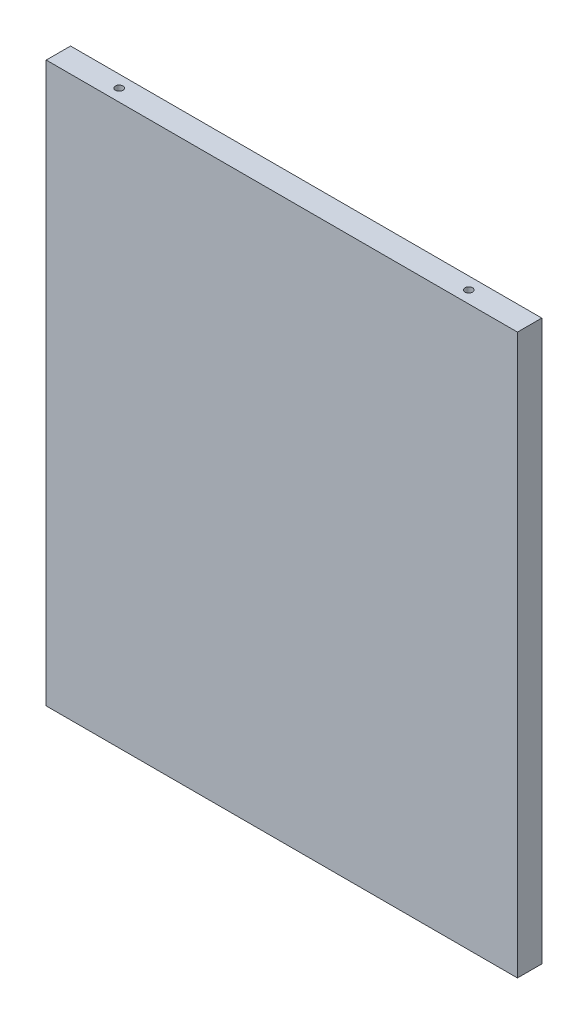
SolidWorks part; units mm, degrees
material "ДСП"
ref_plane "Спереди" through (0, 0, 0) normal (0, 0, 1) x (1, 0, 0)
ref_plane "Сверху" through (0, 0, 0) normal (0, 1, 0) x (1, 0, 0)
ref_plane "Справа" through (0, 0, 0) normal (1, 0, 0) x (0, 0, -1)
sketch "Эскиз1" plane through (0, 0, 0) normal (0, 0, 1) x (1, 0, 0)
  line L1 (0, 0) -> (310, 0)
  line L2 (0, 0) -> (0, 368)
  line L3 (0, 368) -> (310, 368)
  line L4 (310, 0) -> (310, 368)
  dimension "D1" = 368
  dimension "D2" = 310
extrude "Придание толщины" add sketch "Эскиз1" along normal blind 16
sketch "Эскиз3" plane through (0, 0, 16) normal (0, 0, 1) x (1, 0, 0)
  line L0 (0, 368) -> (0, 0) construction
  line L1 (0, 0) -> (310, 0) construction
  circle A0 centre (0, 0) radius 4
  dimension "D1" = 8
  dimension "D2" = 0
  dimension "D3" = 0
extrude "Отверстие 1" [suppressed] cut sketch "Эскиз3" against normal blind 16
sketch "Эскиз4" plane through (0, 0, 16) normal (0, 0, 1) x (1, 0, 0)
  line L0 (0, 368) -> (0, 0) construction
  line L1 (0, 0) -> (310, 0) construction
  circle A0 centre (0, 0) radius 4
  dimension "D2" = 0
  dimension "D3" = 8
extrude "Отверстие 2" [suppressed] cut sketch "Эскиз4" against normal blind 16
sketch "Эскиз5" plane through (0, 0, 16) normal (0, 0, 1) x (1, 0, 0)
  line L0 (0, 368) -> (0, 0) construction
  line L1 (0, 0) -> (310, 0) construction
  circle A0 centre (0, 0) radius 4
  dimension "D1" = 8
extrude "Отверстие 3" [suppressed] cut sketch "Эскиз5" against normal blind 16
sketch "Эскиз6" plane through (0, 0, 16) normal (0, 0, 1) x (1, 0, 0)
  line L0 (0, 368) -> (0, 0) construction
  line L1 (0, 0) -> (310, 0) construction
  circle A0 centre (0, 0) radius 4
  dimension "D1" = 8
extrude "Отверстие 4" [suppressed] cut sketch "Эскиз6" against normal blind 16
sketch "Эскиз7" plane through (0, 0, 16) normal (0, 0, 1) x (1, 0, 0)
  line L0 (0, 368) -> (0, 0) construction
  line L1 (0, 0) -> (310, 0) construction
  circle A0 centre (0, 0) radius 4
  dimension "D1" = 8
extrude "Отверстие 5" [suppressed] cut sketch "Эскиз7" against normal blind 16
sketch "Эскиз8" plane through (0, 0, 16) normal (0, 0, 1) x (1, 0, 0)
  line L0 (0, 368) -> (0, 0) construction
  line L1 (0, 0) -> (310, 0) construction
  circle A0 centre (0, 0) radius 4
  dimension "D1" = 8
extrude "Отверстие 6" [suppressed] cut sketch "Эскиз8" against normal blind 16
sketch "Эскиз9" plane through (0, 0, 16) normal (0, 0, 1) x (1, 0, 0)
  line L0 (0, 368) -> (0, 0) construction
  line L1 (0, 0) -> (310, 0) construction
  circle A0 centre (0, 0) radius 4
  dimension "D1" = 8
extrude "Отверстие 7" [suppressed] cut sketch "Эскиз9" against normal blind 16
sketch "Эскиз10" plane through (0, 0, 16) normal (0, 0, 1) x (1, 0, 0)
  line L0 (0, 368) -> (0, 0) construction
  line L1 (0, 0) -> (310, 0) construction
  circle A0 centre (0, 0) radius 4
  dimension "D1" = 8
extrude "Отверстие 8" [suppressed] cut sketch "Эскиз10" against normal blind 16
sketch "Эскиз27" plane through (0, 0, 16) normal (0, 0, 1) x (1, 0, 0)
  line L2 (0, 368) -> (0, 0) construction
  line L3 (0, 0) -> (310, 0) construction
  circle A0 centre (0, 0) radius 4
  dimension "D1" = 8
  dimension "D3" = 0
extrude "Отверстие 9" [suppressed] cut sketch "Эскиз27" against normal blind 10
sketch "Эскиз29" plane through (0, 0, 16) normal (0, 0, 1) x (1, 0, 0)
  line L2 (0, 368) -> (0, 0) construction
  line L3 (0, 0) -> (310, 0) construction
  circle A0 centre (0, 0) radius 4
  dimension "D1" = 8
extrude "Отверстие 10" [suppressed] cut sketch "Эскиз29" against normal blind 10
sketch "Эскиз30" plane through (0, 0, 16) normal (0, 0, 1) x (1, 0, 0)
  line L1 (0, 0) -> (310, 0) construction
  line L3 (0, 368) -> (0, 0) construction
  circle A0 centre (0, 0) radius 4
  dimension "D1" = 8
extrude "Отверстие 11" [suppressed] cut sketch "Эскиз30" against normal blind 10
sketch "Эскиз31" plane through (0, 0, 16) normal (0, 0, 1) x (1, 0, 0)
  line L2 (0, 0) -> (310, 0) construction
  line L3 (0, 368) -> (0, 0) construction
  circle A0 centre (0, 0) radius 4
  dimension "D1" = 8
extrude "Отверстие 12" [suppressed] cut sketch "Эскиз31" against normal blind 10
sketch "Эскиз11" plane through (0, 368, 0) normal (0, 1, 0) x (1, 0, 0)
  line L0 (0, -16) -> (0, 0) construction
  line L1 (310, -16) -> (0, -16) construction
  circle A0 centre (40, -8) radius 2.5
  dimension "D3" = 8
  dimension "D1" = 5
  dimension "D2" = 40
extrude "Отверстие А1" cut sketch "Эскиз11" against normal blind 37
sketch "Эскиз12" plane through (0, 368, 0) normal (0, 1, 0) x (1, 0, 0)
  line L1 (0, -16) -> (0, 0) construction
  line L2 (310, -16) -> (0, -16) construction
  circle A0 centre (270, -8) radius 2.5
  dimension "D3" = 8
  dimension "D1" = 5
  dimension "D2" = 270
extrude "Отверстие А2" cut sketch "Эскиз12" against normal blind 37
sketch "Эскиз13" plane through (0, 368, 0) normal (0, 1, 0) x (1, 0, 0)
  line L1 (0, -16) -> (0, 0) construction
  line L2 (310, -16) -> (0, -16) construction
  circle A0 centre (0, -16) radius 4
  dimension "D1" = 8
  dimension "D3" = 0
extrude "Отверстие А3" [suppressed] cut sketch "Эскиз13" against normal blind 20
sketch "Эскиз14" plane through (0, 368, 0) normal (0, 1, 0) x (1, 0, 0)
  line L0 (0, -16) -> (0, 0) construction
  line L1 (310, -16) -> (0, -16) construction
  circle A0 centre (0, -8) radius 4
  dimension "D1" = 8
  dimension "D3" = 8
extrude "Отверстие А4" [suppressed] cut sketch "Эскиз14" against normal blind 20
sketch "Эскиз15" plane through (310, 0, 0) normal (1, 0, 0) x (0, 0, -1)
  line L0 (-16, 368) -> (0, 368) construction
  line L1 (-16, 0) -> (-16, 368) construction
  circle A0 centre (-16, 368) radius 2.5
  dimension "D2" = 0
  dimension "D3" = 0
  dimension "D1" = 5
extrude "Отверстие В1" [suppressed] cut sketch "Эскиз15" against normal blind 37
sketch "Эскиз16" plane through (310, 0, 0) normal (1, 0, 0) x (0, 0, -1)
  line L0 (-16, 368) -> (0, 368) construction
  line L1 (-16, 0) -> (-16, 368) construction
  circle A0 centre (-16, 368) radius 2.5
  dimension "D1" = 5
extrude "Отверстие В2" [suppressed] cut sketch "Эскиз16" against normal blind 37
sketch "Эскиз17" plane through (310, 0, 0) normal (1, 0, 0) x (0, 0, -1)
  line L1 (-16, 368) -> (0, 368) construction
  line L2 (-16, 0) -> (-16, 368) construction
  circle A0 centre (-16, 368) radius 4
  dimension "D1" = 8
  dimension "D2" = 0
  dimension "D3" = 0
extrude "Отверстие В3" [suppressed] cut sketch "Эскиз17" against normal blind 20
sketch "Эскиз18" plane through (310, 0, 0) normal (1, 0, 0) x (0, 0, -1)
  line L0 (-16, 368) -> (0, 368) construction
  line L1 (-16, 0) -> (-16, 368) construction
  circle A0 centre (-16, 368) radius 4
  dimension "D3" = 0
  dimension "D1" = 0
  dimension "D2" = 8
extrude "Отверстие В4" [suppressed] cut sketch "Эскиз18" against normal blind 20
sketch "Эскиз19" plane through (0, 0, 0) normal (0, -1, 0) x (1, 0, 0)
  line L0 (310, 16) -> (310, 0) construction
  line L1 (0, 16) -> (310, 16) construction
  circle A0 centre (270, 8) radius 2.5
  dimension "D3" = 8
  dimension "D1" = 5
  dimension "D2" = 40
extrude "Отверстие С1" cut sketch "Эскиз19" against normal blind 37
sketch "Эскиз20" plane through (0, 0, 0) normal (0, -1, 0) x (1, 0, 0)
  line L0 (310, 16) -> (310, 0) construction
  line L1 (0, 16) -> (310, 16) construction
  circle A0 centre (40, 8) radius 2.5
  dimension "D3" = 8
  dimension "D2" = 5
  dimension "D1" = 270
extrude "Отверстие С2" cut sketch "Эскиз20" against normal blind 37
sketch "Эскиз21" plane through (0, 0, 0) normal (0, -1, 0) x (1, 0, 0)
  line L0 (310, 16) -> (310, 0) construction
  line L1 (0, 16) -> (310, 16) construction
  circle A0 centre (310, 16) radius 4
  dimension "D1" = 8
  dimension "D2" = 0
  dimension "D3" = 0
extrude "Отверстие С3" [suppressed] cut sketch "Эскиз21" against normal blind 20
sketch "Эскиз22" plane through (0, 0, 0) normal (0, -1, 0) x (1, 0, 0)
  line L0 (310, 16) -> (310, 0) construction
  line L1 (0, 16) -> (310, 16) construction
  circle A0 centre (310, 16) radius 4
  dimension "D1" = 8
  dimension "D2" = 0
  dimension "D3" = 0
extrude "Отверстие С4" [suppressed] cut sketch "Эскиз22" against normal blind 20
sketch "Эскиз23" plane through (0, 0, 0) normal (-1, 0, 0) x (0, 0, 1)
  line L0 (16, 0) -> (0, 0) construction
  line L1 (16, 368) -> (16, 0) construction
  circle A0 centre (16, 0) radius 2.5
  dimension "D2" = 0
  dimension "D3" = 0
  dimension "D1" = 5
extrude "Отверстие Д1" [suppressed] cut sketch "Эскиз23" against normal blind 37
sketch "Эскиз24" plane through (0, 0, 0) normal (-1, 0, 0) x (0, 0, 1)
  line L0 (16, 0) -> (0, 0) construction
  line L1 (16, 368) -> (16, 0) construction
  circle A0 centre (16, 0) radius 2.5
  dimension "D2" = 0
  dimension "D3" = 0
  dimension "D1" = 5
extrude "Отверстие Д2" [suppressed] cut sketch "Эскиз24" against normal blind 37
sketch "Эскиз25" plane through (0, 0, 0) normal (-1, 0, 0) x (0, 0, 1)
  line L0 (16, 0) -> (0, 0) construction
  line L1 (16, 368) -> (16, 0) construction
  circle A0 centre (16, 0) radius 4
  dimension "D1" = 8
  dimension "D2" = 0
  dimension "D3" = 0
extrude "Отверстие Д3" [suppressed] cut sketch "Эскиз25" against normal blind 20
sketch "Эскиз26" plane through (0, 0, 0) normal (-1, 0, 0) x (0, 0, 1)
  line L0 (16, 0) -> (0, 0) construction
  line L1 (16, 368) -> (16, 0) construction
  circle A0 centre (16, 0) radius 4
  dimension "D1" = 8
  dimension "D2" = 0
  dimension "D3" = 0
extrude "Отверстие Д4" [suppressed] cut sketch "Эскиз26" against normal blind 20
equation "\"D1@Придание толщины\" = \"Thick\""
equation "\"D2@Эскиз1\"=\"Width\""
equation "\"D1@Эскиз1\"=\"Height\""
equation "\"D1\" = 0"
equation "\"X1\" = 0"
equation "\"Y1\" = 0"
equation "\"H1\" = 0"
equation "\"D1@Эскиз3\"=\"D1\""
equation "\"D2@Эскиз3\"=\"X1\""
equation "\"D3@Эскиз3\"=\"Y1\""
equation "\"D1@Отверстие 1\"=\"H1\""
equation "\"D2\" = 0"
equation "\"X2\" = 0"
equation "\"Y2\" = 0"
equation "\"H2\" = 0"
equation "\"D3\" = 0"
equation "\"X3\" = 0"
equation "\"Y3\" = 0"
equation "\"H3\" = 0"
equation "\"D4\" = 0"
equation "\"X4\" = 0"
equation "\"Y4\" = 0"
equation "\"H4\" = 0"
equation "\"D5\" = 0"
equation "\"X5\" = 0"
equation "\"Y5\" = 0"
equation "\"H5\" = 0"
equation "\"D6\" = 0"
equation "\"X6\" = 0"
equation "\"Y6\" = 0"
equation "\"H6\" = 0"
equation "\"D7\" = 0"
equation "\"X7\" = 0"
equation "\"Y7\" = 0"
equation "\"H7\" = 0"
equation "\"D8\" = 0"
equation "\"X8\" = 0"
equation "\"Y8\" = 0"
equation "\"H8\" = 0"
equation "\"D3@Эскиз4\"=\"D2\""
equation "\"D1@Эскиз4\"=\"X2\""
equation "\"D2@Эскиз4\"=\"Y2\""
equation "\"D1@Отверстие 2\"=\"H2\""
equation "\"D2@Эскиз5\"=\"X3\""
equation "\"D1@Эскиз5\"=\"D3\""
equation "\"D3@Эскиз5\"=\"Y3\""
equation "\"D1@Отверстие 3\" = \"H3\""
equation "\"D1@Эскиз6\"=\"D4\""
equation "\"D2@Эскиз6\"=\"X4\""
equation "\"D3@Эскиз6\"=\"Y4\""
equation "\"D1@Отверстие 4\" = \"H4\""
equation "\"D1@Эскиз7\"=\"D5\""
equation "\"D2@Эскиз7\"=\"X5\""
equation "\"D3@Эскиз7\"=\"Y5\""
equation "\"D1@Отверстие 5\" = \"H5\""
equation "\"D1@Эскиз8\"=\"D6\""
equation "\"D2@Эскиз8\"=\"X6\""
equation "\"D3@Эскиз8\"=\"Y6\""
equation "\"D1@Отверстие 6\" = \"H6\""
equation "\"D1@Эскиз9\"=\"D7\""
equation "\"D2@Эскиз9\"=\"X7\""
equation "\"D3@Эскиз9\"=\"Y7\""
equation "\"D1@Отверстие 7\" = \"H7\""
equation "\"D1@Эскиз10\"=\"D8\""
equation "\"D2@Эскиз10\"=\"X8\""
equation "\"D3@Эскиз10\"=\"Y8\""
equation "\"D1@Отверстие 8\" = \"H8\""
equation "\"Отверстие 1\"= IIF ( \"D1\" = 0 , \"suppressed\" , \"unsuppressed\" )"
equation "\"Отверстие 2\"= IIF ( \"D2\" = 0 , \"suppressed\" , \"unsuppressed\" )"
equation "\"Отверстие 3\"= IIF ( \"D3\" = 0 , \"suppressed\" , \"unsuppressed\" )"
equation "\"Отверстие 4\"= IIF ( \"D4\" = 0 , \"suppressed\" , \"unsuppressed\" )"
equation "\"Отверстие 5\"= IIF ( \"D5\" = 0 , \"suppressed\" , \"unsuppressed\" )"
equation "\"Отверстие 6\" = IIF ( \"D6\" = 0 , \"suppressed\" , \"unsuppressed\" )"
equation "\"Отверстие 7\"= IIF ( \"D7\" = 0 , \"suppressed\" , \"unsuppressed\" )"
equation "\"Отверстие 8\"= IIF ( \"D8\" = 0 , \"suppressed\" , \"unsuppressed\" )"
equation "\"DA1\" = 5"
equation "\"XA1\" = 40"
equation "\"YA1\" = 8"
equation "\"HA1\" = 37"
equation "\"DA2\" = 5"
equation "\"XA2\" = 270"
equation "\"YA2\" = 8"
equation "\"HA2\" = 37"
equation "\"DA3\" = 0"
equation "\"XA3\" = 0"
equation "\"YA3\" = 0"
equation "\"DA4\" = 0"
equation "\"XA4\" = 0"
equation "\"YA4\" = 0"
equation "\"HA4\" = 0"
equation "\"D1@Эскиз11\"=\"DA1\""
equation "\"D2@Эскиз11\"=\"XA1\""
equation "\"D3@Эскиз11\"=\"YA1\""
equation "\"D1@Отверстие А1\" = \"HA1\""
equation "\"D1@Эскиз12\"=\"DA2\""
equation "\"D2@Эскиз12\"=\"XA2\""
equation "\"HA3\" = 0"
equation "\"D1@Эскиз13\"=\"DA3\""
equation "\"D2@Эскиз13\"=\"XA3\""
equation "\"D3@Эскиз13\"=\"YA3\""
equation "\"D1@Отверстие А3\" = \"HA3\""
equation "\"D1@Отверстие А2\" = \"HA2\""
equation "\"D1@Эскиз14\"=\"DA4\""
equation "\"D2@Эскиз14\"=\"XA4\""
equation "\"Отверстие А1\"= IIF ( \"DA1\" = 0 , \"suppressed\" , \"unsuppressed\" )"
equation "\"Отверстие А2\"= IIF ( \"DA2\" = 0 , \"suppressed\" , \"unsuppressed\" )"
equation "\"Отверстие А3\"= IIF ( \"DA3\" = 0 , \"suppressed\" , \"unsuppressed\" )"
equation "\"Отверстие А4\"= IIF ( \"DA4\" = 0 , \"suppressed\" , \"unsuppressed\" )"
equation "\"DB1\" = 0"
equation "\"XB1\" = 0"
equation "\"YB1\" = 0"
equation "\"HB1\" = 0"
equation "\"DB2\" = 0"
equation "\"XB2\" = 0"
equation "\"YB2\" = 0"
equation "\"HB2\" = 0"
equation "\"DB3\" = 0"
equation "\"XB3\" = 0"
equation "\"YB3\" = 0"
equation "\"HB3\" = 0"
equation "\"DB4\" = 0"
equation "\"XB4\" = 0"
equation "\"YB4\" = 0"
equation "\"HB4\" = 0"
equation "\"DC1\" = 5"
equation "\"XC1\" = 40"
equation "\"YC1\" = 8"
equation "\"HC1\" = 37"
equation "\"DC2\" = 5"
equation "\"XC2\" = 270"
equation "\"YC2\" = 8"
equation "\"HC2\" = 37"
equation "\"DC3\" = 0"
equation "\"XC3\" = 0"
equation "\"YC3\" = 0"
equation "\"HC3\" = 0"
equation "\"DC4\" = 0"
equation "\"XC4\" = 0"
equation "\"YC4\" = 0"
equation "\"HC4\" = 0"
equation "\"DD1\" = 0"
equation "\"XD1\" = 0"
equation "\"YD1\" = 0"
equation "\"HD1\" = 0"
equation "\"DD2\" = 0"
equation "\"XD2\" = 0"
equation "\"YD2\" = 0"
equation "\"HD2\" = 0"
equation "\"DD3\" = 0"
equation "\"XD3\" = 0"
equation "\"YD3\" = 0"
equation "\"HD3\" = 0"
equation "\"DD4\" = 0"
equation "\"XD4\" = 0"
equation "\"YD4\" = 0"
equation "\"HD4\" = 0"
equation "\"D1@Эскиз15\"=\"DB1\""
equation "\"D2@Эскиз15\"=\"XB1\""
equation "\"D3@Эскиз15\"=\"YB1\""
equation "\"D1@Отверстие В1\" = \"HB1\""
equation "\"D1@Эскиз16\"=\"DB2\""
equation "\"D2@Эскиз16\"=\"XB2\""
equation "\"D3@Эскиз16\"=\"YB2\""
equation "\"D1@Отверстие В2\" = \"HB2\""
equation "\"D1@Эскиз17\"=\"DB3\""
equation "\"D2@Эскиз17\"=\"XB3\""
equation "\"D3@Эскиз17\"=\"YB3\""
equation "\"D1@Отверстие В3\" = \"HB3\""
equation "\"D1@Эскиз18\"=\"XB4\""
equation "\"D2@Эскиз18\"=\"DB4\""
equation "\"D3@Эскиз18\"=\"YB4\""
equation "\"D1@Отверстие В4\" = \"HB4\""
equation "\"D1@Эскиз19\"=\"DC1\""
equation "\"D2@Эскиз19\"=\"XC1\""
equation "\"D3@Эскиз19\"=\"YC1\""
equation "\"D1@Отверстие С1\" = \"HC1\""
equation "\"D1@Эскиз20\"=\"XC2\""
equation "\"D2@Эскиз20\"=\"DC2\""
equation "\"D3@Эскиз20\"=\"YC2\""
equation "\"D1@Отверстие С2\" = \"HC2\""
equation "\"D1@Эскиз21\"=\"DC3\""
equation "\"D2@Эскиз21\"=\"XC3\""
equation "\"D3@Эскиз21\"=\"YC3\""
equation "\"D1@Отверстие С3\" = \"HC3\""
equation "\"D1@Эскиз22\"=\"DC4\""
equation "\"D2@Эскиз22\"=\"XC4\""
equation "\"D3@Эскиз22\"=\"YC4\""
equation "\"D1@Отверстие С4\" = \"HC4\""
equation "\"D1@Эскиз23\"=\"DD1\""
equation "\"D2@Эскиз23\"=\"XD1\""
equation "\"D3@Эскиз23\"=\"YD1\""
equation "\"D1@Отверстие Д1\" = \"HD1\""
equation "\"D1@Эскиз24\"=\"DD2\""
equation "\"D2@Эскиз24\"=\"XD2\""
equation "\"D3@Эскиз24\"=\"YD2\""
equation "\"D1@Отверстие Д2\" = \"HD2\""
equation "\"D1@Эскиз25\"=\"DD3\""
equation "\"D2@Эскиз25\"=\"XD3\""
equation "\"D3@Эскиз25\"=\"YD3\""
equation "\"D1@Отверстие Д3\" = \"HD3\""
equation "\"D1@Эскиз26\"=\"DD4\""
equation "\"D2@Эскиз26\"=\"XD4\""
equation "\"D3@Эскиз26\"=\"YD4\""
equation "\"D1@Отверстие Д4\" = \"HD4\""
equation "\"Отверстие В1\"= IIF ( \"DB1\" = 0 , \"suppressed\" , \"unsuppressed\" )"
equation "\"Отверстие В2\"= IIF ( \"DB2\" = 0 , \"suppressed\" , \"unsuppressed\" )"
equation "\"Отверстие В3\"= IIF ( \"DB3\" = 0 , \"suppressed\" , \"unsuppressed\" )"
equation "\"Отверстие В4\"= IIF ( \"DB4\" = 0 , \"suppressed\" , \"unsuppressed\" )"
equation "\"Отверстие С1\"= IIF ( \"DC1\" = 0 , \"suppressed\" , \"unsuppressed\" )"
equation "\"Отверстие С2\"= IIF ( \"DC2\" = 0 , \"suppressed\" , \"unsuppressed\" )"
equation "\"Отверстие С3\"= IIF ( \"DC3\" = 0 , \"suppressed\" , \"unsuppressed\" )"
equation "\"Отверстие С4\"= IIF ( \"DC4\" = 0 , \"suppressed\" , \"unsuppressed\" )"
equation "\"Отверстие Д1\"= IIF ( \"DD1\" = 0 , \"suppressed\" , \"unsuppressed\" )"
equation "\"Отверстие Д2\"= IIF ( \"DD2\" = 0 , \"suppressed\" , \"unsuppressed\" )"
equation "\"Отверстие Д3\"= IIF ( \"DD3\" = 0 , \"suppressed\" , \"unsuppressed\" )"
equation "\"Отверстие Д4\"= IIF ( \"DD4\" = 0 , \"suppressed\" , \"unsuppressed\" )"
equation "\"D9\" = 0"
equation "\"X9\" = 0"
equation "\"Y9\" = 0"
equation "\"H9\" = 0"
equation "\"D10\" = 0"
equation "\"X10\" = 0"
equation "\"Y10\" = 0"
equation "\"H10\" = 0"
equation "\"D11\" = 0"
equation "\"X11\" = 0"
equation "\"Y11\" = 0"
equation "\"H11\" = 0"
equation "\"D12\" = 0"
equation "\"X12\" = 0"
equation "\"Y12\" = 0"
equation "\"H12\" = 0"
equation "\"D1@Эскиз27\"=\"D9\""
equation "\"D2@Эскиз27\"=\"X9\""
equation "\"D3@Эскиз27\"=\"Y9\""
equation "\"D1@Отверстие 9\" = \"H9\""
equation "\"D1@Эскиз29\"=\"D10\""
equation "\"D2@Эскиз29\"=\"X10\""
equation "\"D3@Эскиз29\"=\"Y10\""
equation "\"D1@Отверстие 10\" = \"H10\""
equation "\"D1@Эскиз30\"=\"D11\""
equation "\"D2@Эскиз30\"=\"X11\""
equation "\"D3@Эскиз30\"=\"Y11\""
equation "\"D1@Отверстие 11\" = \"H11\""
equation "\"D1@Эскиз31\"=\"D12\""
equation "\"D2@Эскиз31\"=\"X12\""
equation "\"D3@Эскиз31\"=\"Y12\""
equation "\"D1@Отверстие 12\" = \"H12\""
equation "\"Отверстие 9\"= IIF ( \"D9\" = 0 , \"suppressed\" , \"unsuppressed\" )"
equation "\"Отверстие 10\"= IIF ( \"D10\" = 0 , \"suppressed\" , \"unsuppressed\" )"
equation "\"Отверстие 11\"= IIF ( \"D11\" = 0 , \"suppressed\" , \"unsuppressed\" )"
equation "\"Отверстие 12\"= IIF ( \"D12\" = 0 , \"suppressed\" , \"unsuppressed\" )"
equation "\"Height\" = 368"
equation "\"Width\" = 310"
equation "\"Thick\" = 16"
equation "\"D3@Эскиз12\"=\"YA2\""
